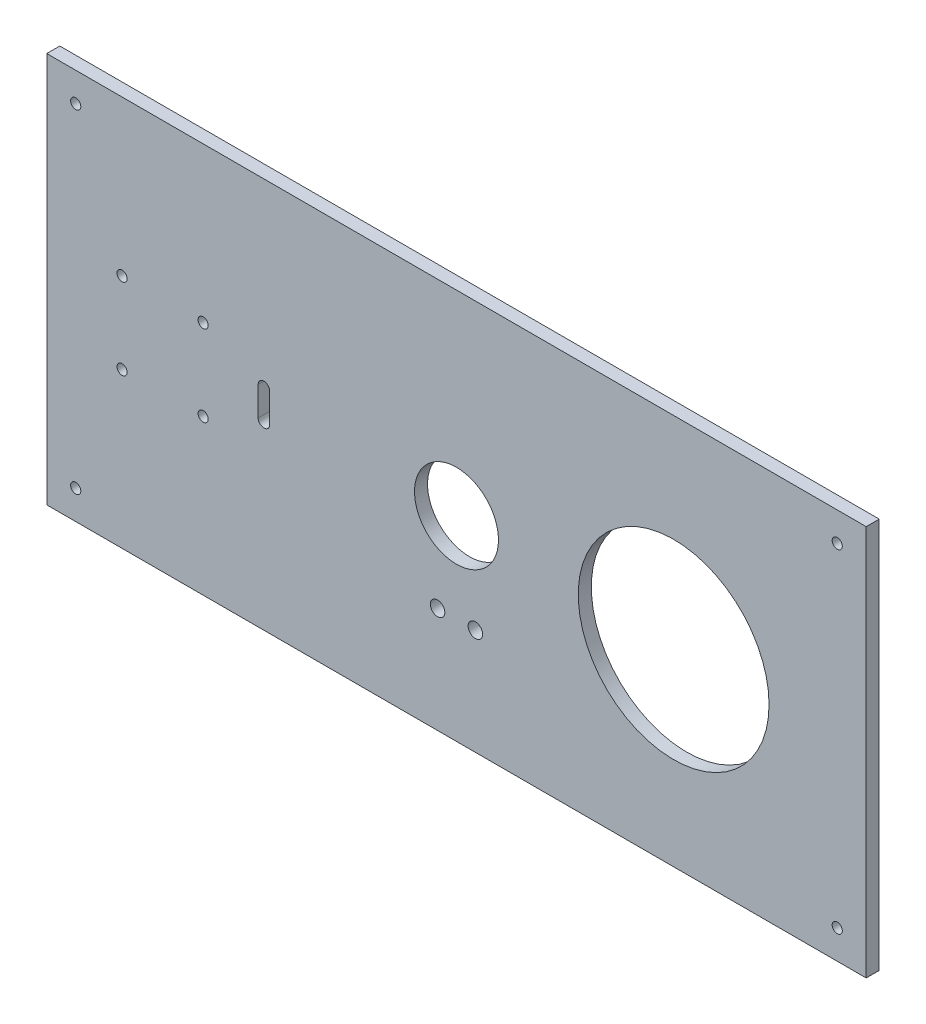
SolidWorks part; units mm, degrees
material "ABS"
ref_plane "Front Plane" through (0, 0, 0) normal (0, 0, 1) x (1, 0, 0)
ref_plane "Top Plane" through (0, 0, 0) normal (0, 1, 0) x (1, 0, 0)
ref_plane "Right Plane" through (0, 0, 0) normal (1, 0, 0) x (0, 0, -1)
sketch "Sketch1" plane through (0, 0, 0) normal (0, 0, 1) x (1, 0, 0)
  line L0 (0, 0) -> (0, 166.746) construction
  line L1 (141.5, -67.5) -> (-141.5, -67.5)
  line L2 (141.5, -67.5) -> (141.5, 67.5)
  line L3 (141.5, 67.5) -> (-141.5, 67.5)
  line L4 (-141.5, -67.5) -> (-141.5, 67.5)
  line L5 (141.5, -67.5) -> (-141.5, 67.5) construction
  line L6 (141.5, 67.5) -> (-141.5, -67.5) construction
  line L7 (0, 0) -> (-259.0657, 0) construction
  circle A0 centre (-131.5, 57.5) radius 1.75
  point P0 (0, 0)
  dimension "D5" = 3.5
  dimension "D1" = 283
  dimension "D2" = 135
  dimension "D3" = 57.5
  dimension "D4" = 131.5
extrude "Boss-Extrude1" add sketch "Sketch1" along normal blind 4.5 contours L4 L1 L2 L3 A0 | A0 region at (0.0331, -0.0145, 0) region at (-131.5, 57.5, 0)
extrude "Cut-Extrude1" cut sketch "Sketch1<3>" along normal up to next contours A0
sketch "Sketch1<3>" plane through (0, 0, 0) normal (0, 0, 1) x (1, 0, 0) same geometry as "Sketch1"
mirror "Mirror2" about plane through (0, 0, 0) normal (0, 1, 0) of "Cut-Extrude1"
mirror "Mirror3" about plane through (0, 0, 0) normal (1, 0, 0) of "Mirror2"
sketch "Sketch2" plane through (0, 0, 4.5) normal (0, 0, 1) x (1, 0, 0)
  line L0 (-115.5, 14) -> (-114.2626, 12.7626) construction
  line L1 (-87.5, 14) -> (-88.7374, 12.7626) construction
  line L4 (-88.7374, -12.7626) -> (-87.5, -14) construction
  line L5 (-114.2626, -12.7626) -> (-115.5, -14) construction
  line L6 (-115.5, 14) -> (-115.5, -14) construction
  line L7 (-115.5, -14) -> (-87.5, -14) construction
  line L8 (-87.5, -14) -> (-87.5, 14) construction
  line L9 (-87.5, 14) -> (-115.5, 14) construction
  line L11 (141.5, -67.5) -> (-141.5, -67.5) construction
  line L12 (-141.5, -67.5) -> (-141.5, 67.5) construction
  line L13 (0, 0) -> (-101.5, 0) construction
  line L14 (-66.5, -5) -> (-66.5, 5) construction
  line L15 (-68.5, -5) -> (-68.5, 5)
  line L16 (-64.5, -5) -> (-64.5, 5)
  circle A0 centre (-87.5, -14) radius 1.75
  circle A1 centre (-115.5, -14) radius 1.75
  circle A2 centre (-115.5, 14) radius 1.75
  circle A3 centre (-87.5, 14) radius 1.75
  arc A4 (-68.5, -5) -> (-64.5, -5) centre (-66.5, -5) ccw
  arc A5 (-64.5, 5) -> (-68.5, 5) centre (-66.5, 5) ccw
  point P14 (-66.5, 0)
  dimension "D1" = 28
  dimension "D8" = 35
  dimension "D9" = 10
  dimension "D3" = 3.5
  dimension "D7" = 2
  dimension "D2" = 28
  dimension "D4" = 26
  dimension "D5" = 14
  dimension "D6" = 14
extrude "Cut-Extrude2" cut sketch "Sketch2" against normal up to next
sketch "Sketch3" plane through (0, 0, 4.5) normal (0, 0, 1) x (1, 0, 0)
  line L0 (75, -2.5) -> (75, 30.45) construction
  line L1 (141.5, -67.5) -> (-141.5, -67.5) construction
  line L2 (-6.525, -30.95) -> (6.525, -30.95) construction
  line L3 (0, 0) -> (0, -30.95) construction
  circle A0 centre (75, -2.5) radius 32.95
  circle A1 centre (0, 0) radius 14.5
  circle A2 centre (-6.525, -30.95) radius 2.5
  circle A3 centre (6.525, -30.95) radius 2.5
  point P12 (0, 0)
  point P14 (0, -30.95)
  point P15 (0, -13.8434)
  dimension "D1" = 65.9
  dimension "D3" = 65
  dimension "D4" = 29
  dimension "D6" = 5
  dimension "D2" = 75
  dimension "D5" = 13.05
  dimension "D7" = 30.95
extrude "Cut-Extrude3" cut sketch "Sketch3" against normal up to next
